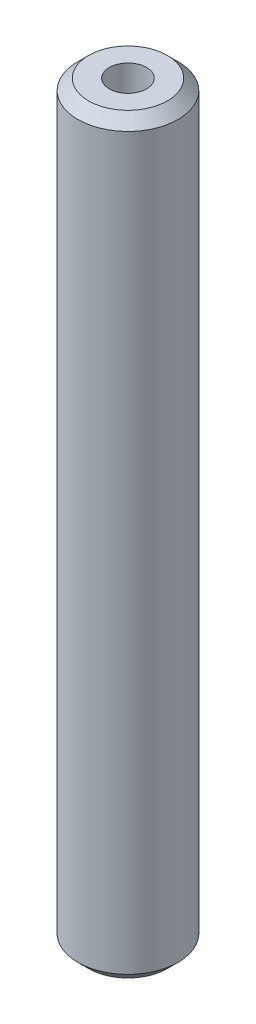
SolidWorks part; units mm, degrees
ref_plane "Front Plane" through (0, 0, 0) normal (0, 0, 1) x (1, 0, 0)
ref_plane "Top Plane" through (0, 0, 0) normal (0, 1, 0) x (1, 0, 0)
ref_plane "Right Plane" through (0, 0, 0) normal (1, 0, 0) x (0, 0, -1)
sketch "Sketch1" plane through (0, 0, 0) normal (0, 1, 0) x (1, 0, 0)
  circle A0 centre (0, 0) radius 25
  dimension "SHAFT_OD" = 50
extrude "Boss-Extrude1" add sketch "Sketch1" along normal blind 374.823
sketch "Sketch2" plane through (0, 0, 0) normal (0, 1, 0) x (1, 0, 0)
  circle A0 centre (0, 0) radius 9.2868
  dimension "BORE_D" = 18.5737
extrude "Cut-Extrude1" cut sketch "Sketch2" along normal through all
chamfer "Chamfer1" distance 5.3464 angle 45 2 edges at (0, 374.823, 25) (0, 0, 25)
